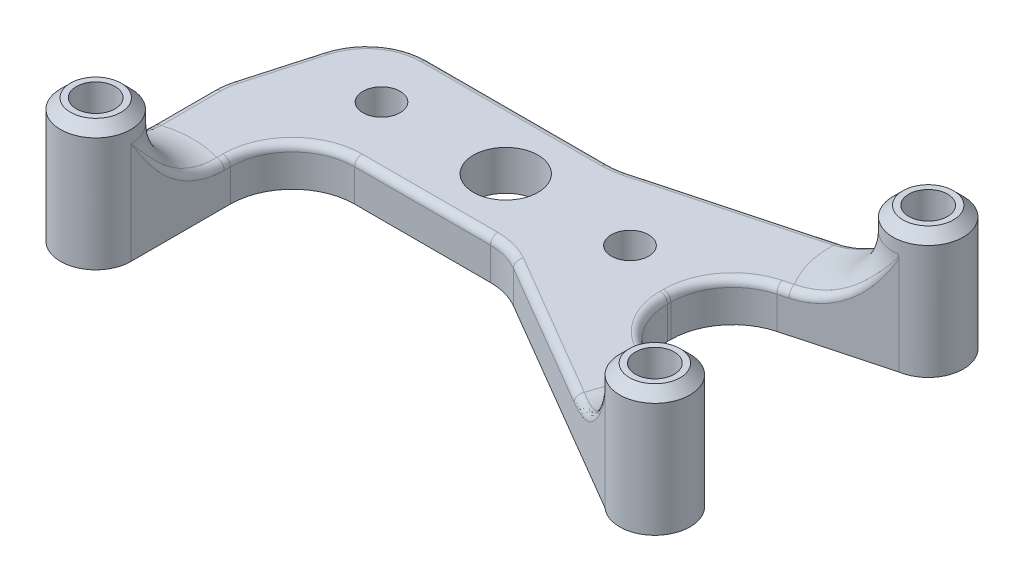
SolidWorks part; units mm, degrees
ref_plane "Front Plane" through (0, 0, 0) normal (0, 0, 1) x (1, 0, 0)
ref_plane "Top Plane" through (0, 0, 0) normal (0, 1, 0) x (1, 0, 0)
ref_plane "Right Plane" through (0, 0, 0) normal (1, 0, 0) x (0, 0, -1)
sketch "Sketch6" plane through (0, 0, 0) normal (0, 1, 0) x (1, 0, 0)
  line L1 (-19.05, -6.35) -> (19.05, -6.35)
  line L2 (-19.05, -6.35) -> (-19.05, 6.35)
  line L3 (-19.05, 6.35) -> (19.05, 6.35)
  line L4 (19.05, -6.35) -> (19.05, 6.35)
  line L5 (-19.05, -6.35) -> (19.05, 6.35) construction
  line L6 (-19.05, 6.35) -> (19.05, -6.35) construction
  point P0 (0, 0)
  dimension "D1" = 12.7
  dimension "D2" = 38.1
extrude "Boss-Extrude6" add sketch "Sketch6" along normal blind 3.175 separate body
sketch "Sketch4" plane through (0, 0, 0) normal (0, 1, 0) x (1, 0, 0)
  circle A0 centre (-19.05, -22.86) radius 3.6
  circle A1 centre (33.02, -17.78) radius 3.6
  circle A2 centre (33.02, 10.16) radius 3.6
  dimension "D1" = 7.2
  dimension "D2" = 7.2
  dimension "D3" = 7.2
  dimension "D4" = 52.07
  dimension "D5" = 5.08
  dimension "D6" = 27.94
  dimension "D7" = 10.16
  dimension "D8" = 33.02
extrude "Boss-Extrude5" add sketch "Sketch4" along normal blind 12.7
sketch "Sketch8" plane through (0, 0, 0) normal (0, 1, 0) x (1, 0, 0)
  line L2 (31.8384, 13.5606) -> (5.0632, 6.35)
  line L3 (19.05, 6.35) -> (-19.05, 6.35) construction
  line L4 (33.5862, 6.6048) -> (19.05, 2.6902)
  line L5 (19.05, -6.35) -> (19.05, 6.35) construction
  line L6 (19.05, 2.6902) -> (19.05, -6.35)
  line L7 (19.05, -6.35) -> (34.6277, -14.5589)
  line L8 (30.6114, -20.4556) -> (6.515, -6.35)
  line L9 (-19.05, -6.35) -> (19.05, -6.35) construction
  line L10 (6.515, -6.35) -> (-15.45, -6.35)
  line L11 (-15.45, -6.35) -> (-15.45, -22.86)
  line L12 (-22.65, -22.86) -> (-22.65, -6.35)
  line L13 (-22.65, -6.35) -> (-19.05, 6.35)
  line L14 (-19.05, 6.35) -> (5.0632, 6.35)
  circle A0 centre (33.02, 10.16) radius 3.6 construction
  arc A1 (33.5862, 6.6048) -> (31.8384, 13.5606) centre (33.02, 10.16) ccw
  circle A2 centre (33.02, -17.78) radius 3.6 construction
  arc A3 (34.6277, -14.5589) -> (30.6114, -20.4556) centre (33.02, -17.78) cw
  circle A4 centre (-19.05, -22.86) radius 3.6 construction
  arc A5 (-15.45, -22.86) -> (-22.65, -22.86) centre (-19.05, -22.86) cw
extrude "Boss-Extrude7" add sketch "Sketch8" along normal blind 4.064
fillet "Fillet1" radius 6.35 7 edges at (-15.45, 2.032, 6.35) (6.515, 2.032, 6.35) (19.05, 2.032, 6.35) (19.05, 2.032, -2.6902) (5.0632, 2.032, -6.35) (-22.65, 2.032, 6.35) (-19.05, 2.032, -6.35)
sketch "Sketch9" plane through (0, 4.064, 0) normal (0, 1, 0) x (1, 0, 0)
  circle A0 centre (-12.7, 0) radius 1.905
  circle A1 centre (12.7, 0) radius 1.905
  circle A2 centre (0, 0) radius 3.302
  dimension "D3" = 3.81
  dimension "D4" = 3.81
  dimension "D5" = 6.604
  dimension "D1" = 25.4
  dimension "D2" = 12.7
extrude "Cut-Extrude3" cut sketch "Sketch9" against normal through all
fillet "Fillet2" radius 6.35 3 edges at (-19.05, 4.064, 19.26) (30.0446, 4.064, 15.7534) (29.5285, 4.064, -9.2827)
sketch "Sketch10" plane through (0, 12.7, 0) normal (0, 1, 0) x (1, 0, 0)
  circle A0 centre (-19.05, -22.86) radius 1.9812
  circle A1 centre (33.02, -17.78) radius 1.9812
  circle A2 centre (33.02, 10.16) radius 1.9812
  dimension "D1" = 3.9624
  dimension "D2" = 3.9624
  dimension "D3" = 3.9624
extrude "Cut-Extrude4" cut sketch "Sketch10" against normal blind 4.7752
chamfer "Chamfer1" distance 1.016 angle 45 3 edges at (33.02, 12.7, -6.56) (33.02, 12.7, 21.38) (-19.05, 12.7, 26.46)
fillet "Fillet3" radius 0.762 23 edges at (34.1822, 9.6509, 14.3242) (24.4655, 4.064, 9.2038) (33.042, 9.2814, -6.4582) (24.3677, 4.064, -4.1223) (20.3598, 4.064, -1.6865) (19.05, 4.064, 2.3472) (30.8667, 8.8079, -13.2989) (14.5002, 4.064, -8.8914) (5.0559, 4.064, -6.4048) (-22.65, 5.6615, 18.3911) (-22.65, 4.064, 10.4084) (-22.5895, 4.064, 6.3584) (-21.3842, 4.064, 1.8845) (-18.079, 4.064, -5.0655) (-15.45, 5.6615, 18.3911) (-15.45, 4.064, 13.142) (-13.5901, 4.064, 8.2099) (29.7882, 8.4666, 19.9737) (15.605, 4.064, 11.6711) (6.455, 4.064, 6.5713) (19.9631, 4.064, 5.7991) (-5.0133, 4.064, -6.35) (-2.1535, 4.064, 6.35)
sketch "Sketch11" plane through (0, 7.9248, 0) normal (0, 1, 0) x (1, 0, 0)
  circle A0 centre (-19.05, -22.86) radius 1.5875
  circle A1 centre (33.02, -17.78) radius 1.5875
  circle A2 centre (33.02, 10.16) radius 1.5875
  dimension "D1" = 3.175
  dimension "D2" = 3.175
  dimension "D3" = 3.175
extrude "Cut-Extrude5" cut sketch "Sketch11" against normal through all
